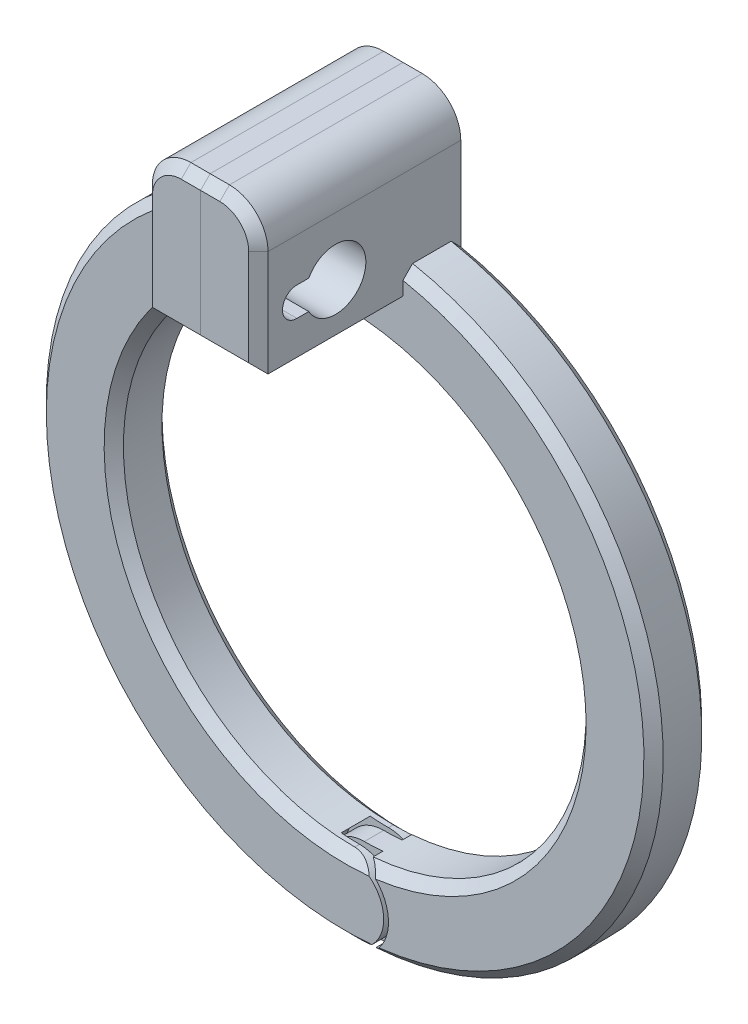
SolidWorks part; units mm, degrees
ref_plane "Ebene vorne" through (0, 0, 0) normal (0, 0, 1) x (1, 0, 0)
ref_plane "Ebene oben" through (0, 0, 0) normal (0, 1, 0) x (1, 0, 0)
ref_plane "Ebene rechts" through (0, 0, 0) normal (1, 0, 0) x (0, 0, -1)
sketch "Skizze1" plane through (0, 0, 0) normal (0, 0, 1) x (1, 0, 0)
  line L1 (0, -32) -> (0, -8) construction
  line L2 (0, -8) -> (0, 0)
  arc A0 (0, -8) -> (0, -56) centre (0, -32) ccw
  arc A1 (0, -56) -> (0, -64) centre (0, -60) cw
  arc A2 (0, -64) -> (0, 0) centre (0, -32) cw
  dimension "D1" = 4
  dimension "D2" = 24
extrude "Aufsatz-Linear austragen1" add sketch "Skizze1" along normal mid plane 6
sketch "Skizze2" plane through (0, 0, 0) normal (0, 0, 1) x (1, 0, 0)
  circle A0 centre (0, -60) radius 4.5
  dimension "D1" = 9
extrude "Schnitt-Linear austragen1" cut sketch "Skizze2" against normal mid plane 3
sketch "Skizze3" plane through (0, 0, 0) normal (0, 0, 1) x (1, 0, 0)
  circle A0 centre (0, -60) radius 2
  dimension "D1" = 4
extrude "Aufsatz-Linear austragen2" add sketch "Skizze3" along normal up to surface and the other way up to surface up to face at (-0.6383, -59.949, 1.5) other way up to face at (-0.6383, -59.949, -1.5)
sketch "Skizze4" plane through (0, 0, 0) normal (0, 0, 1) x (1, 0, 0)
  line L0 (0, -32) -> (0, -8) construction
  line L1 (0, -8) -> (0, 0)
  arc A0 (0, -8) -> (0, -56) centre (0, -32) cw
  arc A1 (0, 0) -> (0, -64) centre (0, -32) cw
  arc A2 (0, -56) -> (0, -64) centre (0, -60) ccw
  arc A3 (0, -8) -> (0, -56) centre (0, -32) ccw construction
  arc A4 (0, 0) -> (0, -64) centre (0, -32) ccw construction
  circle A5 centre (0, -60) radius 2.5
  dimension "D2" = 5
extrude "Aufsatz-Linear austragen4" add sketch "Skizze4" along normal mid plane 6 separate body
sketch "Skizze5" plane through (0, 0, 3) normal (0, 0, 1) x (1, 0, 0)
  circle A0 centre (0, -60) radius 4.5
  dimension "D1" = 9
extrude "Schnitt-Linear austragen2" cut sketch "Skizze5" against normal blind 2
mirror "Spiegeln1" about plane through (0, 0, 0) normal (0, 0, 1) of "Schnitt-Linear austragen2"
sketch "Skizze6" plane through (0, 0, -3) normal (0, 0, -1) x (-1, 0, 0)
  line L0 (0, 0) -> (0, 12)
  line L1 (0, 0) -> (0, -8) construction
  line L2 (0, 12) -> (-2, 12)
  line L3 (-6, 8) -> (-6, -0.5675)
  arc A0 (-2, 12) -> (-6, 8) centre (-2, 8) ccw
  arc A1 (0, 0) -> (-2.2026, -63.9241) centre (0, -32) ccw construction
  arc A2 (0, 0) -> (-6, -0.5675) centre (0, -32) ccw
  dimension "D1" = 6
  dimension "D2" = 2
  dimension "D3" = 12
extrude "Aufsatz-Linear austragen5" add sketch "Skizze6" against normal up to surface (6 mm away) up to face at (15.1147, -31.4444, 3)
sketch "Skizze7" plane through (0, 0, -3) normal (0, 0, -1) x (-1, 0, 0)
  line L0 (0, 0) -> (0, 12)
  line L1 (0, 12) -> (2, 12)
  line L2 (6, 8) -> (6, -0.5675)
  line L3 (0, -8) -> (0, 0) construction
  arc A0 (2, 12) -> (6, 8) centre (2, 8) cw
  arc A1 (0, -64) -> (0, 0) centre (0, -32) ccw construction
  arc A2 (6, -0.5675) -> (0, 0) centre (0, -32) ccw
  dimension "D1" = 2
  dimension "D2" = 12
  dimension "D3" = 6
extrude "Aufsatz-Linear austragen6" add sketch "Skizze7" against normal up to surface (6 mm away) up to face at (-13, -32, 3)
sketch "Skizze8" plane through (0, 0, 3) normal (0, 0, 1) x (1, 0, 0)
  line L0 (0, -3) -> (6, -3)
  line L3 (6, -0.5675) -> (6, 8)
  line L4 (2, 12) -> (0, 12)
  line L5 (0, 12) -> (0, -8)
  line L6 (6, -3) -> (6, 8)
  line L7 (2, 12) -> (0, 12)
  line L8 (0, 12) -> (0, -3)
  arc A4 (1.9071, -55.9241) -> (0, -8) centre (0, -32) ccw
  arc A5 (2.2026, -63.9241) -> (1.9071, -55.9241) centre (0, -60) ccw
  arc A6 (2.2026, -63.9241) -> (6, -0.5675) centre (0, -32) ccw
  arc A7 (6, 8) -> (2, 12) centre (2, 8) ccw
  arc A11 (6, 8) -> (2, 12) centre (2, 8) ccw
  dimension "D2" = 15
  dimension "D1" = 0
extrude "Aufsatz-Linear austragen7" add sketch "Skizze8" along normal blind 15
sketch "Skizze9" plane through (0, 0, 3) normal (0, 0, 1) x (1, 0, 0)
  line L2 (0, -3) -> (-6, -3)
  line L5 (0, -8) -> (0, 12)
  line L6 (0, 12) -> (-2, 12)
  line L14 (-6, 8) -> (-6, -0.5675)
  line L15 (0, -3) -> (0, 12)
  line L16 (0, 12) -> (-2, 12)
  line L17 (-6, 8) -> (-6, -3)
  arc A4 (0, -8) -> (0, -56) centre (0, -32) ccw
  arc A5 (-2, 12) -> (-6, 8) centre (-2, 8) ccw
  arc A6 (-6, -0.5675) -> (0, -64) centre (0, -32) ccw
  arc A7 (0, -64) -> (0, -56) centre (0, -60) ccw
  arc A16 (0, -8) -> (0, -56) centre (0, -32) ccw
  arc A17 (-2, 12) -> (-6, 8) centre (-2, 8) ccw
  line M10 (0, -8) -> (0, 12)
  line M12 (0, 12) -> (-2, 12)
  arc M13 (-2, 12) -> (-6, 8) centre (-2, 8) ccw
  line M14 (-6, 8) -> (-6, -0.5675)
  dimension "D2" = 15
  dimension "D1" = 0
extrude "Aufsatz-Linear austragen9" add sketch "Skizze9" along normal up to surface (15 mm away) contours L2 M10 M12 M13 M14 region at (-2.9164, 4.238, 3) up to face at (2.9657, 5.3657, 18)
sketch "Skizze10" plane through (0, 0, 0) normal (1, 0, 0) x (0, 0, -1)
  line L0 (-18, -3) -> (-18, 8) construction
  line L1 (-18, -3) -> (-3, -3) construction
  line L2 (-10, 2) -> (-14, 2) construction
  line L3 (-12.7699, 3.5) -> (-14, 3.5)
  line L4 (-12.7699, 0.5) -> (-14, 0.5)
  circle A0 centre (-10, 2) radius 3.15
  arc A1 (-14, 3.5) -> (-14, 0.5) centre (-14, 2) ccw
  dimension "D1" = 6.3
  dimension "D5" = 1.5
  dimension "D2" = 8
  dimension "D3" = 5
  dimension "D4" = 4
extrude "Schnitt-Linear austragen3" cut sketch "Skizze10" against normal mid plane 13 contours A0 | L3 A1 L4 A0 region at (0, 2, 14.1254) region at (0, 2, 10)
chamfer "Fase1" distance 1 angle 45 2 edges at (23.981, -31.0457, 3) (23.981, -31.0457, -3)
chamfer "Fase2" distance 1 angle 45 2 edges at (-24, -32, 3) (-24, -32, -3) tangent propagation no
chamfer "Fase3" distance 1 angle 45 2 edges at (31.9427, -33.9146, 3) (31.9427, -33.9146, -3)
chamfer "Fase4" distance 1 angle 45 2 edges at (-31.8578, -35.0134, 3) (-31.8578, -35.0134, -3) tangent propagation no
chamfer "Fase5" distance 1 angle 45 4 edges at (1, 12, 18) (4.8284, 10.8284, 18) (3, -3, 18) (6, 2.5, 18)
chamfer "Fase6" distance 1 angle 45 4 edges at (-1, 12, 18) (-3, -3, 18) (-6, 2.5, 18) (-4.8284, 10.8284, 18)
